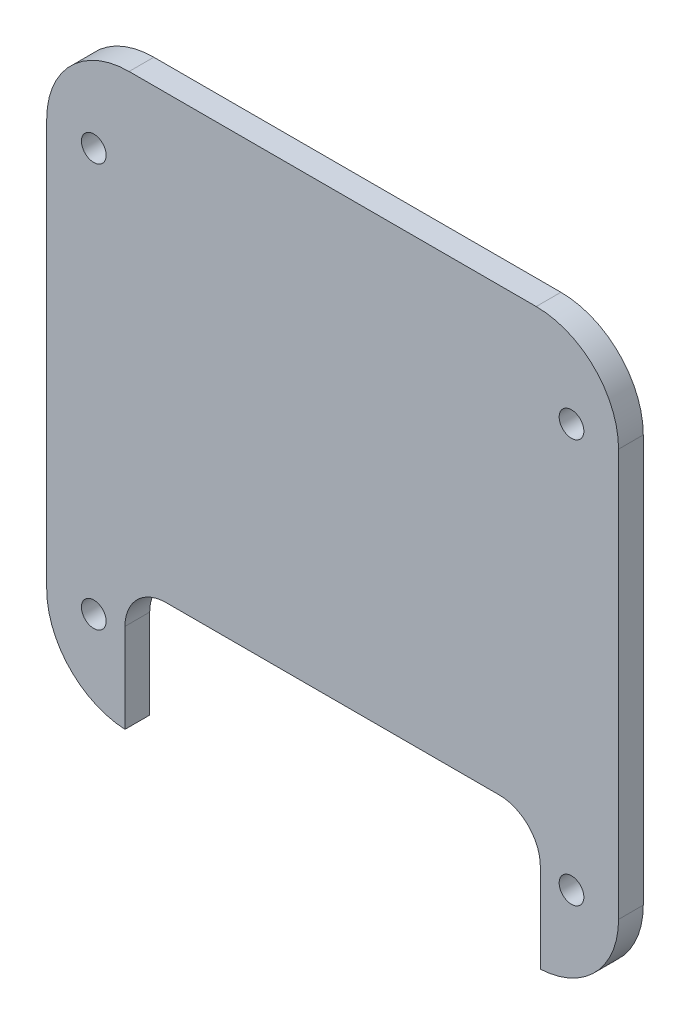
SolidWorks part; units mm, degrees
ref_plane "Front Plane" through (0, 0, 0) normal (0, 0, 1) x (1, 0, 0)
ref_plane "Top Plane" through (0, 0, 0) normal (0, 1, 0) x (1, 0, 0)
ref_plane "Right Plane" through (0, 0, 0) normal (1, 0, 0) x (0, 0, -1)
sketch "Sketch1" plane through (0, 0, 0) normal (0, 0, 1) x (1, 0, 0)
  line L1 (-34.7154, -34.7154) -> (34.7154, -34.7154)
  line L2 (-34.7154, -34.7154) -> (-34.7154, 34.7154)
  line L3 (-34.7154, 34.7154) -> (34.7154, 34.7154)
  line L4 (34.7154, -34.7154) -> (34.7154, 34.7154)
  line L5 (-34.7154, -34.7154) -> (34.7154, 34.7154) construction
  line L6 (-34.7154, 34.7154) -> (34.7154, -34.7154) construction
  point P0 (0, 0)
  point P6 (32.2889, 32.2889)
  point P7 (0, 0)
  point P8 (0, 0)
  point P9 (35.4249, 35.4249)
  point P10 (34.7154, 34.7154)
extrude "Boss-Extrude2" add sketch "Sketch1" along normal blind 3
sketch "Sketch6" plane through (0, 0, 3) normal (0, 0, 1) x (1, 0, 0)
  line L0 (29, 24.5) -> (29, 34.7154) construction
  line L1 (29, 24.5) -> (-29, 24.5) construction
  line L2 (29, -24.5) -> (-29, -24.5) construction
  line L4 (-29, -24.5) -> (-29, 24.5) construction
  line L5 (-25.2154, -34.7154) -> (-25.2154, -18.8892)
  line L69 (34.7154, 34.7154) -> (-34.7154, 34.7154) construction
  line L70 (29, -24.5) -> (29, -34.7154) construction
  line L71 (-34.7154, -34.7154) -> (34.7154, -34.7154) construction
  line L72 (-29, 24.5) -> (-34.7154, 24.5) construction
  line L73 (-34.7154, 34.7154) -> (-34.7154, -34.7154) construction
  line L74 (29, 24.5) -> (34.7154, 24.5) construction
  line L75 (34.7154, -34.7154) -> (34.7154, 34.7154) construction
  line L76 (-25.2154, -18.8892) -> (25.2154, -18.8892)
  line L77 (25.2154, -18.8892) -> (25.2154, -34.7154)
  line L78 (-25.2154, -34.7154) -> (25.2154, -34.7154)
  line L79 (-34.7154, -34.7154) -> (-25.2154, -34.7154) construction
  line L80 (25.2154, -34.7154) -> (34.7154, -34.7154) construction
  circle A16 centre (-29, 24.5) radius 1.5
  circle A17 centre (-29, -24.5) radius 1.5
  circle A18 centre (29, -24.5) radius 1.5
  circle A19 centre (29, 24.5) radius 1.5
  dimension "D1" = 58
  dimension "D3" = 9.5
  dimension "D2" = 49
  dimension "D4" = 15.8262
  dimension "D5" = 3
extrude "Cut-Extrude1" cut sketch "Sketch6" against normal blind 10
fillet "Fillet1" radius 10 1 edges at (34.7154, 34.7154, 1.5)
fillet "Fillet2" radius 10 3 edges at (34.7154, -34.7154, 1.5) (-34.7154, -34.7154, 1.5) (-34.7154, 34.7154, 1.5)
fillet "Fillet3" radius 4.9946 2 edges at (25.2154, -18.8892, 1.5) (-25.2154, -18.8892, 1.5)
